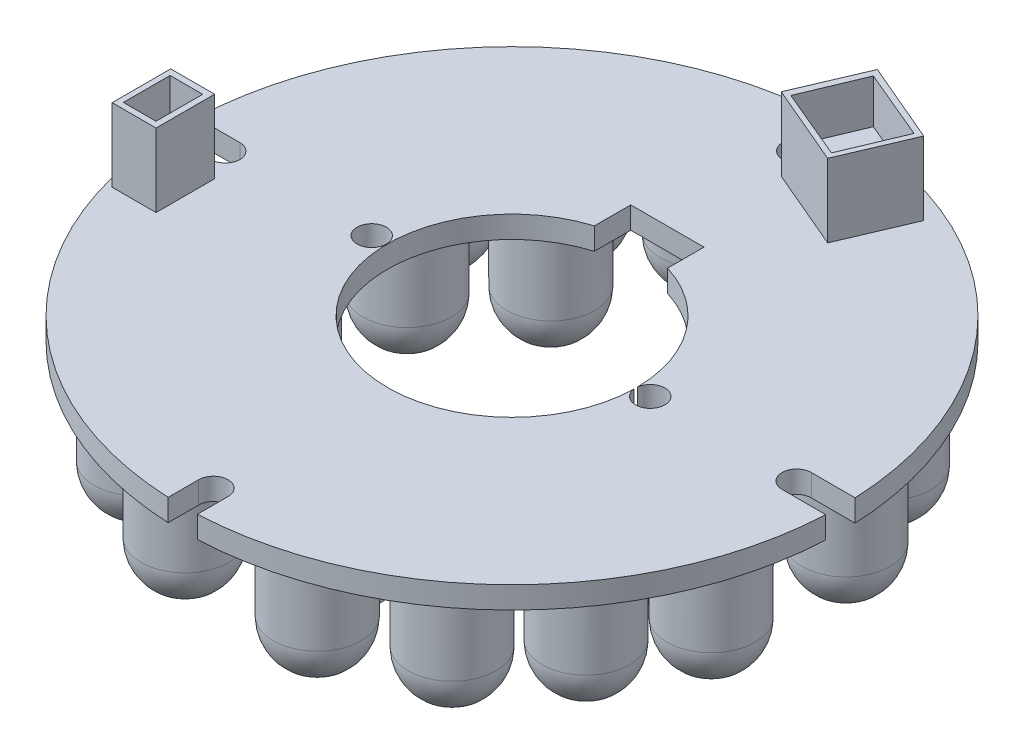
SolidWorks part; units mm, degrees
material "Plain Carbon Steel"
ref_plane "Front Plane" through (0, 0, 0) normal (0, 0, 1) x (1, 0, 0)
ref_plane "Top Plane" through (0, 0, 0) normal (0, 1, 0) x (1, 0, 0)
ref_plane "Right Plane" through (0, 0, 0) normal (1, 0, 0) x (0, 0, -1)
sketch "Sketch1" plane through (0, 0, 0) normal (0, 1, 0) x (1, 0, 0)
  line L0 (-19.525, -1.0538) -> (-22.4753, -1.0538)
  line L1 (-19.525, 0.9462) -> (-22.4801, 0.9462)
  line L2 (19.4935, 0.9462) -> (22.4801, 0.9462)
  line L3 (19.4935, -1.0538) -> (22.4753, -1.0538)
  line L4 (-2.5, 10.6072) -> (2.5, 10.6072)
  line L5 (-1, 22.4778) -> (-1, 19.4778)
  line L6 (1, 19.4778) -> (1, 22.4778)
  line L7 (-2.5, 10.6072) -> (-2.5, 8.124)
  line L8 (2.5, 10.6072) -> (2.5, 8.124)
  line L9 (-1, -20.3928) -> (-1, -22.4778)
  line L10 (1, -20.3928) -> (1, -22.4778)
  circle A0 centre (0, 0) radius 22.5
  circle A1 centre (0, 0) radius 8.5
  circle A2 centre (-9.525, -0.0538) radius 1
  circle A4 centre (9.4935, -0.0538) radius 1
  circle A5 centre (-19.525, -0.0538) radius 1
  arc A6 (-19.525, 0.9462) -> (-19.525, -1.0538) centre (-19.525, -0.0538) ccw
  circle A8 centre (19.4935, -0.0538) radius 1
  circle A10 centre (0, -20.3928) radius 1
  circle A11 centre (0, 19.4778) radius 1
  dimension "D1" = 45
  dimension "D2" = 17
  dimension "D3" = 2
  dimension "D6" = 2
  dimension "D8" = 2
  dimension "D4" = 10
  dimension "D5" = 10
  dimension "D7" = 3
  dimension "D9" = 31
extrude "Boss-Extrude1" add sketch "Sketch1" along normal blind 1.5 contours A0
extrude "Cut-Extrude1" cut sketch "Sketch1<4>" along normal blind 10 contours A5 L1 A0 L0 | A5 | A2 | A1 A4 | A8 | A8 L3 A0 L2 | A10 L9 A0 L10 | A11 L6 A0 L5 | A11 | A4 A1 | A1 L8 L4 L7 | A10 | A1 region at (-21.3901, 0, 0.0535) region at (-19.525, 0, 0.0538) region at (0, 0, 21.8165) region at (0, 0, -21.3667) region at (0, 0, -19.4778) region at (21.3745, 0, 0.0535) region at (19.4935, 0, 0.0538) region at (0, 0, -9.4887) region at (0, 0, 0) region at (9.4938, 0, 0.0538) region at (-9.525, 0, 0.0538)
sketch "Sketch1<4>" plane through (0, 0, 0) normal (0, 1, 0) x (1, 0, 0) same geometry as "Sketch1"
sketch "Sketch3" plane through (0, 1.5, 0) normal (0, 1, 0) x (1, 0, 0)
  line L0 (2.9128, 22.0353) -> (0.9523, 17.4357)
  line L1 (0.9523, 17.4357) -> (6.4719, 15.0831)
  line L3 (2.9128, 22.0353) -> (8.4324, 19.6827)
  line L4 (8.4324, 19.6827) -> (6.4719, 15.0831)
  line L5 (-22.4753, -1.0538) -> (-19.525, -1.0538) construction
  line L6 (-21.2504, -2.0538) -> (-18.2504, -2.0538)
  line L7 (-21.2504, -2.0538) -> (-21.2504, -6.0538)
  line L8 (-21.2504, -6.0538) -> (-18.2504, -6.0538)
  line L9 (-18.2504, -2.0538) -> (-18.2504, -6.0538)
  point P10 (0, 0)
  point P11 (8.6025, 19.5466)
  dimension "D1" = 5
  dimension "D2" = 6
  dimension "D3" = 4
  dimension "D4" = 3
  dimension "D5" = 1
extrude "Boss-Extrude2" add sketch "Sketch3" along normal blind 5
sketch "Sketch4" plane through (0, 0, 0) normal (0, -1, 0) x (1, 0, 0)
  circle A0 centre (0, 12.0951) radius 3
  circle A2 centre (-4.5733, 17.7516) radius 3
  circle A3 centre (4.5733, 17.8719) radius 3
  circle A4 centre (10.9518, 15.0437) radius 3
  circle A5 centre (6.7998, 9.7483) radius 3
  circle A6 centre (18.1126, 4.5131) radius 3
  circle A7 centre (15.1641, 10.1094) radius 3
  circle A8 centre (11.1925, 4.814) radius 3
  circle A9 centre (18.233, -4.5733) radius 3
  circle A10 centre (11.1925, -4.6335) radius 3
  circle A11 centre (15.1039, -10.5306) radius 3
  circle A12 centre (6.6794, -9.989) radius 3
  circle A13 centre (9.0864, -16.3676) radius 3
  circle A14 centre (2.1663, -14.7428) radius 3
  circle A15 centre (-4.8742, -17.9923) radius 3
  circle A16 centre (-10.9518, -14.9234) radius 3
  circle A17 centre (-6.9803, -9.628) radius 3
  circle A18 centre (-11.4934, -4.3326) radius 3
  circle A19 centre (-18.1728, -4.3326) radius 3
  circle A20 centre (-15.1641, -10.0492) radius 3
  circle A21 centre (-14.9835, 1.023) radius 3
  circle A22 centre (-10.3501, 5.5361) radius 3
  circle A23 centre (-16.9091, 7.5219) radius 3
  circle A24 centre (-5.9573, 10.0492) radius 3
  circle A25 centre (-10.7111, 14.803) radius 3
  dimension "D1" = 6
extrude "Boss-Extrude3" add sketch "Sketch4" along normal blind 8
fillet "Fillet1" radius 3 24 edges at (2.1663, -8, -17.7428) (6.6794, -8, -12.989) (9.0864, -8, -19.3676) (15.1039, -8, -13.5306) (11.1925, -8, -7.6335) (18.233, -8, -7.5733) (18.1126, -8, 1.5131) (11.1925, -8, 1.814) (15.1641, -8, 7.1094) (10.9518, -8, 12.0437) (6.7998, -8, 6.7483) (4.5733, -8, 14.8719) (-4.5733, -8, 14.7516) (-10.7111, -8, 11.803) (-5.9573, -8, 7.0492) (-16.9091, -8, 4.5219) (-10.3501, -8, 2.5361) (-14.9835, -8, -1.977) (-18.1728, -8, -7.3326) (-11.4934, -8, -7.3326) (-6.9803, -8, -12.628) (-4.8742, -8, -20.9923) (-10.9518, -8, -17.9234) (-15.1641, -8, -13.0492)
sketch "Sketch5" plane through (0, -8, 0) normal (0, -1, 0) x (1, 0, 0)
  circle A0 centre (0, 12.0647) radius 2.4376
  point P2 (0, 0)
  point P3 (0, 12.0647)
extrude "Cut-Extrude2" cut sketch "Sketch5" against normal blind 1 contours A0
sketch "Sketch6" plane through (0, 6.5, 0) normal (0, 1, 0) x (1, 0, 0)
  line L0 (1.4947, 17.5425) -> (3.1613, 21.5138)
  line L1 (-20.8807, -2.4672) -> (-18.6542, -2.4672)
  line L2 (-20.8807, -2.4672) -> (-20.8807, -5.6564)
  line L3 (-20.8807, -5.6564) -> (-18.6542, -5.6564)
  line L4 (-18.6542, -2.4672) -> (-18.6542, -5.6564)
  line L5 (3.1613, 21.5138) -> (7.9466, 19.5057)
  line L6 (7.9466, 19.5057) -> (6.2801, 15.5343)
  line L7 (6.2801, 15.5343) -> (1.4947, 17.5425)
extrude "Cut-Extrude3" cut sketch "Sketch6" against normal blind 3
